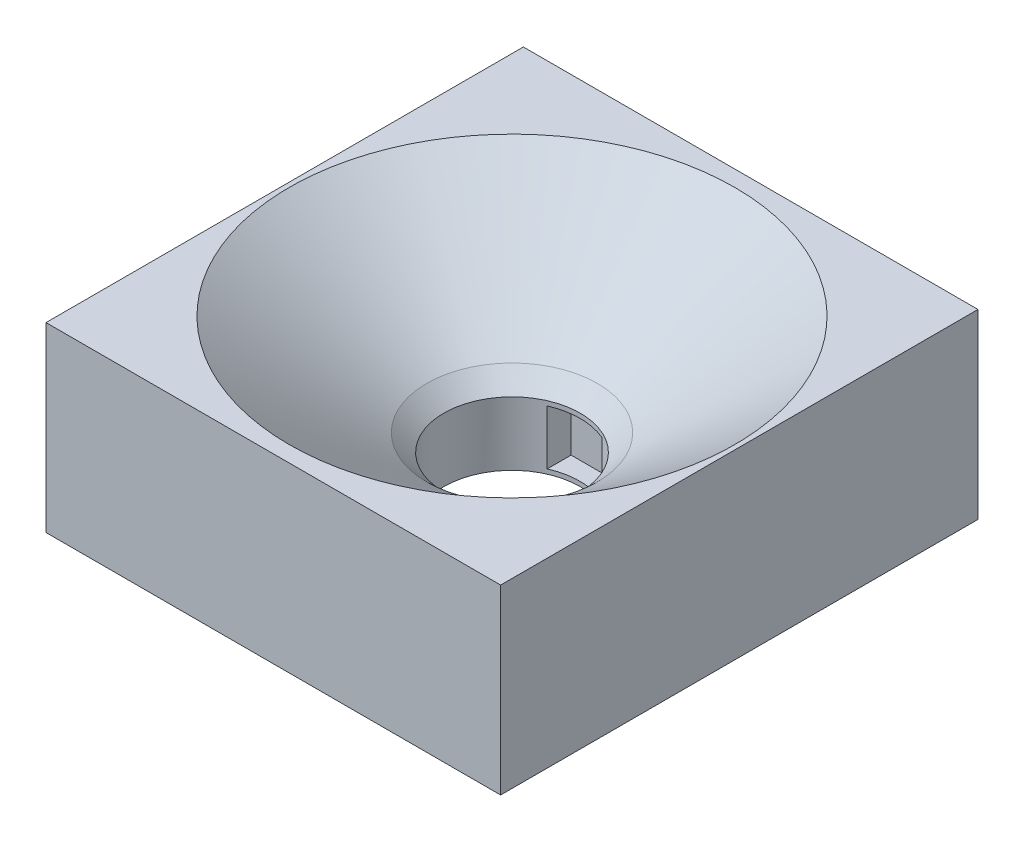
SolidWorks part; units mm, degrees
ref_plane "Front Plane" through (0, 0, 0) normal (0, 0, 1) x (1, 0, 0)
ref_plane "Top Plane" through (0, 0, 0) normal (0, 1, 0) x (1, 0, 0)
ref_plane "Right Plane" through (0, 0, 0) normal (1, 0, 0) x (0, 0, -1)
sketch "Sketch1" plane through (0, 0, 0) normal (0, 1, 0) x (1, 0, 0)
  line L0 (0, -81.1722) -> (0, 92.799) construction
  line L1 (-50, 52.5) -> (50, 52.5)
  line L2 (-50, 52.5) -> (-50, -52.5)
  line L3 (-50, -52.5) -> (50, -52.5)
  line L4 (50, 52.5) -> (50, -52.5)
  line L5 (-86.3397, 0) -> (134.3541, 0) construction
  dimension "D1" = 100
  dimension "D2" = 105
extrude "Boss-Extrude1" add sketch "Sketch1" along normal blind 25
sketch "Sketch5" plane through (0, 0, 0) normal (1, 0, 0) x (0, 0, -1)
  line L0 (0, -20.2311) -> (0, 46.6063) construction
  line L1 (-49, 25) -> (-15, 0)
  line L2 (-52.5, 0) -> (52.5, 0) construction
  line L3 (-15, 0) -> (0, 0)
  line L4 (0, 0) -> (0, 25)
  line L5 (-52.5, 25) -> (52.5, 25) construction
  line L6 (0, 25) -> (-49, 25)
  dimension "D1" = 15
  dimension "D2" = 36.327
  dimension "D3" = 49
revolve "Cut-Revolve1" cut sketch "Sketch5" angle 360 about L0
sketch "Sketch10" plane through (0, 0, 0) normal (0, -1, 0) x (1, 0, 0)
  line L4 (-50, 52.5) -> (-50, -52.5)
  line L5 (-50, -52.5) -> (50, -52.5)
  line L6 (50, -52.5) -> (50, 52.5)
  line L7 (50, 52.5) -> (-50, 52.5)
  line L8 (-50, 52.5) -> (-50, -52.5)
  line L9 (-50, -52.5) -> (50, -52.5)
  line L10 (50, -52.5) -> (50, 52.5)
  line L11 (50, 52.5) -> (-50, 52.5)
  circle A0 centre (0, 0) radius 15 construction
  circle A1 centre (0, 0) radius 15
  dimension "D1" = 0
extrude "Boss-Extrude2" add sketch "Sketch10" along normal blind 15
sketch "Sketch8" plane through (0, -15, 0) normal (0, -1, 0) x (1, 0, 0)
  line L0 (0, 0) -> (0, 56.1231) construction
  line L1 (-17.3, 49.1191) -> (5.2, 49.1191)
  line L2 (-17.3, 49.1191) -> (-17.3, 36.6191)
  line L3 (-17.3, 36.6191) -> (5.2, 36.6191)
  line L4 (5.2, 49.1191) -> (5.2, 36.6191)
  dimension "D1" = 22.5
  dimension "D2" = 12.5
  dimension "D3" = 5.2
extrude "Cut-Extrude4" cut sketch "Sketch8" against normal blind 30
sketch "Sketch9" plane through (0, -15, 0) normal (0, -1, 0) x (1, 0, 0)
  line L2 (-22.8, 49.1191) -> (-22.8, 36.6191)
  line L3 (-22.8, 36.6191) -> (10.7, 36.6191)
  line L4 (10.7, 49.1191) -> (10.7, 36.6191)
  line L5 (-17.3, 36.6191) -> (5.2, 36.6191) construction
  line L6 (-17.3, 49.1191) -> (-17.3, 36.6191) construction
  line L7 (5.2, 36.6191) -> (5.2, 49.1191) construction
  line L8 (-22.8, 49.1191) -> (10.7, 49.1191)
  line L9 (5.2, 49.1191) -> (-17.3, 49.1191) construction
  dimension "D1" = 5.5
  dimension "D2" = 5.5
extrude "Cut-Extrude5" cut sketch "Sketch9" against normal blind 12
chamfer "Chamfer2" distance 1 angle 45 1 edges at (0, 0, -15) first distance on face at (0, -15, -15)
sketch "Sketch13" plane through (0, 0, 0) normal (0, 0, 1) x (1, 0, 0)
  line L0 (-56.5662, -1) -> (61.5672, -1) construction
  line L1 (15, -1) -> (-15, -1) construction
  line L2 (0, 35.5069) -> (0, -41.596) construction
  line L3 (-6, -2) -> (6, -2)
  line L4 (-6, -2) -> (-6, -14)
  line L5 (-6, -14) -> (6, -14)
  line L6 (6, -2) -> (6, -14)
  line L7 (-59.0237, -8) -> (64.6572, -8) construction
  dimension "D1" = 12
  dimension "D2" = 12
  dimension "D3" = 7
extrude "Cut-Extrude10" cut sketch "Sketch13" against normal blind 19
ref_plane "Plane2" through (0, 0, 12) normal (0, 0, 1) x (1, 0, 0)
sketch "Sketch15" plane through (0, 0, 12) normal (0, 0, 1) x (1, 0, 0)
  line L0 (0, 35.4186) -> (0, -39.3949) construction
  line L5 (-70.8325, 14) -> (81.2743, 14) construction
  line L6 (50, -15) -> (-50, -15) construction
  line L7 (-57.8126, -7) -> (75.1932, -7) construction
  circle A0 centre (0, -7) radius 6
  dimension "D1" = 12
  dimension "D3" = 29
  dimension "D4" = 21
extrude "Cut-Extrude11" cut sketch "Sketch15" along normal blind 10
